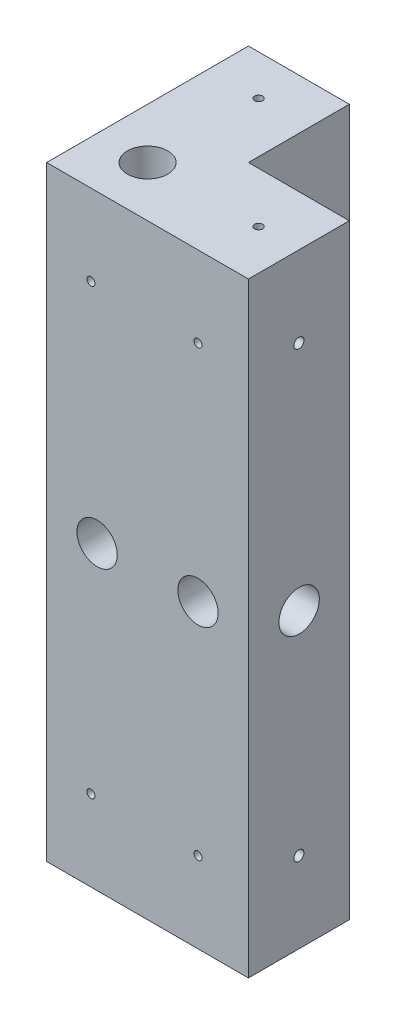
SolidWorks part; units mm, degrees
ref_plane "Front Plane" through (0, 0, 0) normal (0, 0, 1) x (1, 0, 0)
ref_plane "Top Plane" through (0, 0, 0) normal (0, 1, 0) x (1, 0, 0)
ref_plane "Right Plane" through (0, 0, 0) normal (1, 0, 0) x (0, 0, -1)
sketch "Sketch1" plane through (0, 0, 0) normal (0, 1, 0) x (1, 0, 0)
  line L2 (0, 0) -> (0, 50)
  line L3 (0, 50) -> (25, 50)
  line L4 (25, 25) -> (25, 50)
  line L5 (0, 0) -> (50, 0)
  line L7 (25, 25) -> (50, 25)
  line L8 (50, 0) -> (50, 25)
  dimension "D1" = 50
  dimension "D2" = 50
  dimension "D3" = 25
  dimension "D4" = 25
extrude "Boss-Extrude1" add sketch "Sketch1" along normal blind 150
sketch "Sketch2" plane through (0, 0, 0) normal (1, 0, 0) x (0, 0, -1)
  circle A0 centre (12.5, 130) radius 1.25
  circle A1 centre (12.5, 20) radius 1.25
  circle A2 centre (12.5553, 72.54) radius 5
  circle A3 centre (37.5, 130) radius 1.25
  circle A4 centre (37.5, 20) radius 1.25
  circle A5 centre (38.9697, 72.54) radius 5
  dimension "D1" = 2.5
  dimension "D2" = 2.5
  dimension "D3" = 10
  dimension "D6" = 2.5
  dimension "D7" = 2.5
  dimension "D8" = 10
  dimension "D4" = 20
  dimension "D5" = 20
  dimension "D9" = 12.5
  dimension "D10" = 12.5
  dimension "D11" = 12.5
  dimension "D12" = 12.5
  dimension "D13" = 25
extrude "Cut-Extrude1" cut sketch "Sketch2" against normal blind 150 and the other way blind 150
sketch "Sketch3" plane through (0, 0, 0) normal (0, 1, 0) x (1, 0, 0)
  circle A0 centre (12.5, 40) radius 1
  circle A1 centre (40, 12.5) radius 1
  circle A2 centre (12.5, 12.5) radius 5
  dimension "D1" = 2
  dimension "D2" = 2
  dimension "D7" = 10
  dimension "D3" = 10
  dimension "D4" = 12.5
  dimension "D5" = 12.5
  dimension "D6" = 10
extrude "Cut-Extrude2" cut sketch "Sketch3" against normal blind 150 and the other way blind 150
ref_plane "Plane2" through (0, 0, -25) normal (0, 0, -1) x (-1, 0, 0)
sketch "Sketch4" plane through (0, 0, -25) normal (0, 0, -1) x (-1, 0, 0)
  circle A0 centre (-37.5, 130) radius 1
  circle A1 centre (-37.5, 20) radius 1
  circle A2 centre (-37.5, 74.5225) radius 5
  circle A3 centre (-12.5, 74.5225) radius 5
  dimension "D1" = 2
  dimension "D2" = 10
  dimension "2mm" = 2
  dimension "D7" = 10
  dimension "D3" = 12.5
  dimension "D4" = 12.5
  dimension "D5" = 20
  dimension "D6" = 20
  dimension "D8" = 12.5
extrude "Cut-Extrude3" cut sketch "Sketch4" against normal blind 150 and the other way blind 150
sketch "Sketch5" plane through (0, 0, -25) normal (0, 0, -1) x (-1, 0, 0)
  circle A0 centre (-10.9808, 130) radius 1
  circle A1 centre (-10.9808, 20) radius 1
  dimension "D1" = 2
  dimension "D2" = 2
extrude "Cut-Extrude4" cut sketch "Sketch5" against normal blind 150
extrude "Cut-Extrude5" cut sketch "Sketch5<2>" against normal blind 150 and the other way blind 150
sketch "Sketch5<2>" plane through (0, 0, -25) normal (0, 0, -1) x (-1, 0, 0) same geometry as "Sketch5"
